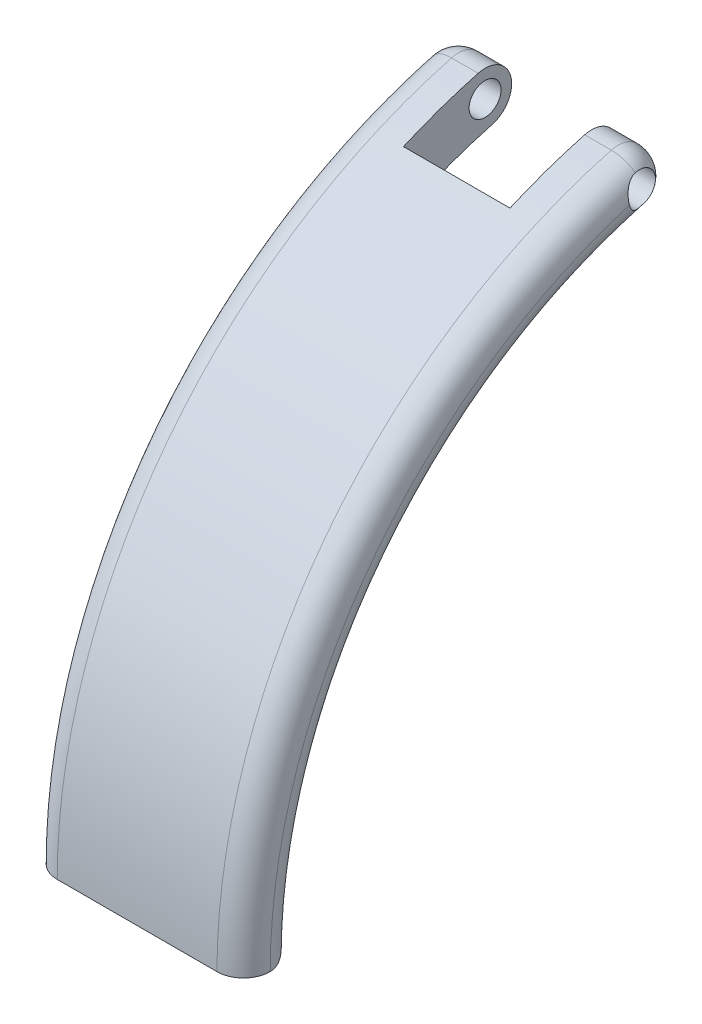
SolidWorks part; units mm, degrees
ref_plane "Front Plane" through (0, 0, 0) normal (0, 0, 1) x (1, 0, 0)
ref_plane "Top Plane" through (0, 0, 0) normal (0, 1, 0) x (1, 0, 0)
ref_plane "Right Plane" through (0, 0, 0) normal (1, 0, 0) x (0, 0, -1)
sketch "Sketch2" plane through (0, 0, 0) normal (1, 0, 0) x (0, 0, -1)
  line L0 (-50, 0) -> (-45, 0)
  line L1 (45, 0) -> (50, 0)
  arc A0 (45, 0) -> (-45, 0) centre (0, 0) ccw
  arc A1 (50, 0) -> (-50, 0) centre (0, 0) ccw
  dimension "D1" = 45
  dimension "D2" = 50
extrude "Boss-Extrude1" add sketch "Sketch2" along normal blind 20
sketch "Sketch3" plane through (0, 0, 0) normal (1, 0, 0) x (0, 0, -1)
  line L0 (0, 45) -> (8, 45)
  line L1 (8, 45) -> (8, 50)
  line L2 (8, 50) -> (-8, 50)
  line L3 (-8, 50) -> (-8, 45)
  line L4 (-8, 45) -> (0, 45)
  arc A0 (45, 0) -> (-45, 0) centre (0, 0) ccw construction
  dimension "D1" = 8
  dimension "D2" = 16
extrude "Boss-Extrude2" add sketch "Sketch3" along normal blind 20
sketch "Sketch4" plane through (0, 50, 0) normal (0, 1, 0) x (1, 0, 0)
  circle A0 centre (10, 0) radius 5
  dimension "D1" = 10
extrude "Cut-Extrude1" cut sketch "Sketch4" against normal blind 2
sketch "Sketch5" plane through (0, 48, 0) normal (0, 1, 0) x (1, 0, 0)
  circle A0 centre (10, 0) radius 7
  dimension "D1" = 14
extrude "Cut-Extrude2" cut sketch "Sketch5" against normal blind 2
sketch "Sketch9" plane through (0, 0, 0) normal (-1, 0, 0) x (0, 0, 1)
  line L0 (10, 46.9468) -> (11.0417, 51.8371)
  line L1 (0, 53) -> (0, 48)
  arc A0 (0, 48) -> (10, 46.9468) centre (0, 0) cw
  arc A1 (11.0417, 51.8371) -> (0, 53) centre (0, 0) ccw
  dimension "D2" = 48
  dimension "D1" = 10
  dimension "D3" = 5
extrude "Boss-Extrude5" add sketch "Sketch9" along normal blind 5
sketch "Sketch10" plane through (-5, 0, 0) normal (-1, 0, 0) x (0, 0, 1)
  line L0 (10, 46.9468) -> (10.4167, 48.9029) construction
  line L1 (10, 46.9468) -> (11.6667, 54.7712)
  line L2 (0, 56) -> (0, 48)
  arc A0 (0, 48) -> (10, 46.9468) centre (0, 0) cw
  arc A1 (11.6667, 54.7712) -> (0, 56) centre (0, 0) ccw
  dimension "D1" = 8
extrude "Boss-Extrude6" add sketch "Sketch10" along normal blind 2
sketch "Sketch11" plane through (0, 0, 0) normal (-1, 0, 0) x (0, 0, 1)
  line L0 (10, 46.9468) -> (9.375, 44.0126) construction
  arc A0 (45, 0) -> (-45, 0) centre (0, 0) ccw construction
  arc A1 (-45, 0) -> (9.375, 44.0126) centre (0, 0) cw
sketch "Sketch12" plane through (0, 0, 0) normal (0, -1, 0) x (1, 0, 0)
  line L1 (0, -50) -> (20, -50)
  line L2 (0, -50) -> (0, -45)
  line L3 (0, -45) -> (20, -45)
  line L4 (20, -50) -> (20, -45)
sweep "Cut-Sweep1" cut profiles "Sketch12" path "Sketch11" body kept at (0, 0, 50)
sketch "Sketch13" plane through (0, 0, 0) normal (0, 0.2083, -0.9781) x (-1, 0, 0)
  line L0 (-20, 45) -> (0, 45) construction
  line L1 (-10, 45) -> (-15, 45)
  line L2 (-10, 45) -> (-10, 50)
  line L3 (-10, 50) -> (-15, 50)
  line L4 (-15, 45) -> (-15, 50)
  line L5 (0, 50) -> (-20, 50) construction
  dimension "D1" = 5
extrude "Cut-Extrude3" cut sketch "Sketch13" against normal blind 10
sketch "Sketch14" plane through (0, 44.0126, 9.375) normal (0, 0.9781, 0.2083) x (1, 0, 0)
  line L1 (15, 0) -> (10, 0)
  line L2 (15, 0) -> (15, -10)
  line L3 (15, -10) -> (10, -10)
  line L4 (10, 0) -> (10, -10)
extrude "Cut-Extrude4" cut sketch "Sketch14" against normal up to next
sketch "Sketch15" plane through (15, 0, 0) normal (-1, 0, 0) x (0, 0, 1)
  line L0 (9.375, 44.0126) -> (10.4167, 48.9029) construction
  line L1 (12.3264, 45.8728) -> (0, 0) construction
  circle A0 centre (12.3264, 45.8728) radius 1.5
  point P2 (9.8958, 46.4577)
  dimension "D1" = 3
  dimension "D2" = 2.5
  dimension "D3" = 47.5
extrude "Cut-Extrude5" cut sketch "Sketch15" against normal up to next
mirror "Mirror1" about plane through (10, 41.9293, 19.1556) normal (-1, 0, 0) of "Cut-Extrude5", "Cut-Extrude4", "Cut-Extrude3"
fillet "Fillet1" radius 2.5 4 edges at (17.5, 48.9029, 10.4167) (17.5, 44.0126, 9.375) (2.5, 44.0126, 9.375) (2.5, 48.9029, 10.4167)
fillet "Fillet2" radius 2.5 9 edges at (20, 30.4236, 39.6787) (20, 48.0049, 11.0223) (20, 44.5675, 10.1949) (0, 30.4236, 39.6787) (0, 48.0049, 11.0223) (0, 44.5675, 10.1949) (10, 0, 45) (20, 27.3813, 35.7109) (0, 27.3813, 35.7109)
